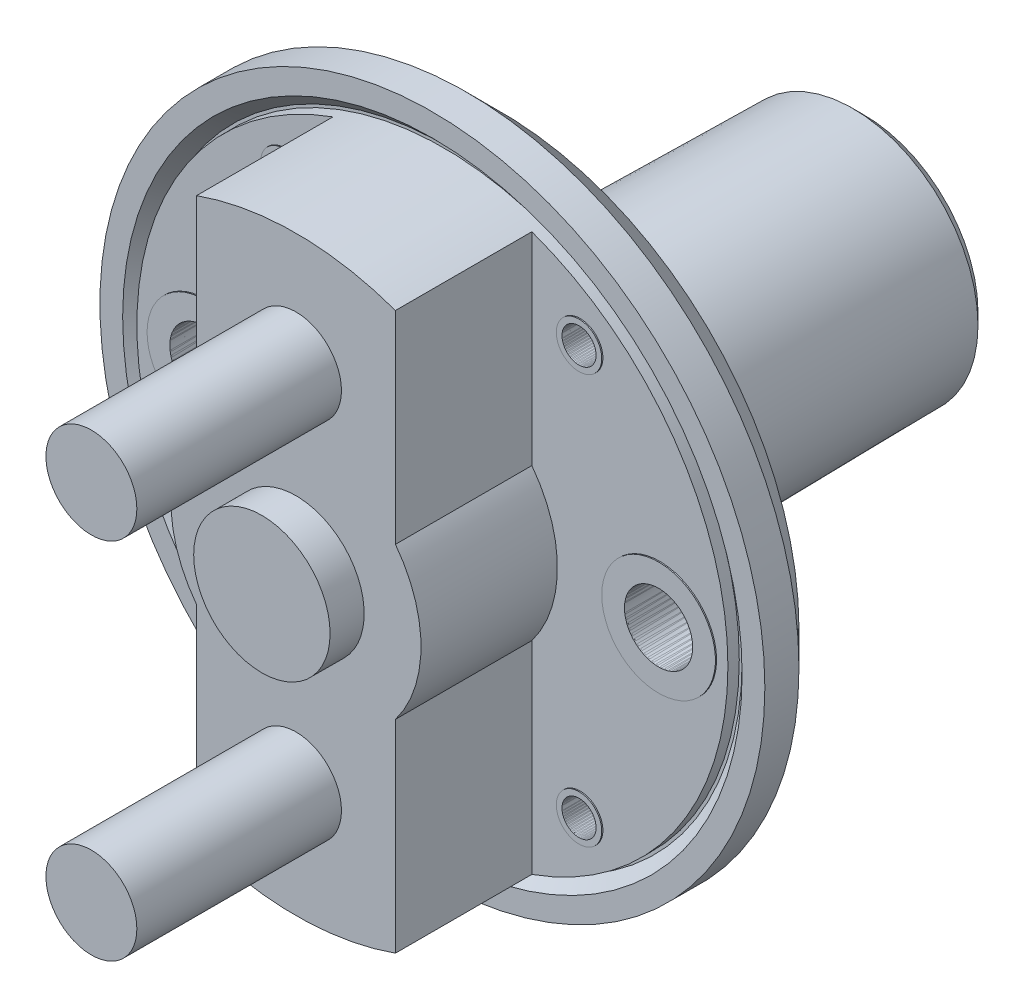
SolidWorks part; units mm, degrees
material "ABS"
ref_plane "正面" through (0, 0, 0) normal (0, 0, 1) x (1, 0, 0)
ref_plane "平面" through (0, 0, 0) normal (0, 1, 0) x (1, 0, 0)
ref_plane "右側面" through (0, 0, 0) normal (1, 0, 0) x (0, 0, -1)
sketch "ｽｹｯﾁ1" plane through (0, 0, 0) normal (0, 0, 1) x (1, 0, 0)
  circle A0 centre (0, 0) radius 11
ref_plane "平面1" through (0, 0, 32) normal (0, 0, 1) x (1, 0, 0)
sketch "ｽｹｯﾁ2" plane through (0, 0, 32) normal (0, 0, 1) x (1, 0, 0)
  circle A0 centre (0, 0) radius 11.5
loft "ﾛﾌﾄ1" add profiles "ｽｹｯﾁ1", "ｽｹｯﾁ2" connector at (1.2963, 10.9233, 0) connector at (0.0939, 11.4996, 32)
sketch "ｽｹｯﾁ3" plane through (0, 0, 0) normal (0, 0, -1) x (-1, 0, 0)
  line L0 (0, 0) -> (2.5, 0) construction
  line L1 (0, 0) -> (-2.5, 0) construction
  line L2 (-2.5, 0) -> (-2.5, -4.899) construction
  line L3 (2.5, 0) -> (2.5, -4.899) construction
  line L4 (-2.5, -4.899) -> (-2.5, -7.899)
  line L5 (-2.5, -7.899) -> (2.5, -7.899)
  line L6 (2.5, -7.899) -> (2.5, -4.899)
  circle A0 centre (0, 0) radius 5.5
extrude "ｶｯﾄ - 押し出し1" cut sketch "ｽｹｯﾁ3" against normal blind 14.5 contours A0 | A0 L4 L5 L6 region at (0, -6.5955, 0) region at (0, 0, 0)
chamfer "面取り1" distance 1 angle 45 1 edges at (11, 0, 0) first distance on face at (0, -3.7992, 0)
chamfer "面取り2" distance 0.5 angle 45 4 edges at (-2.5, -6.399, 0) (0, -7.899, 0) (2.5, -6.399, 0) (0, 5.5, 0)
sketch "ｽｹｯﾁ4" plane through (0, 0, 32) normal (0, 0, 1) x (1, 0, 0)
  circle A0 centre (0, 0) radius 29.25
extrude "ﾎﾞｽ - 押し出し1" add sketch "ｽｹｯﾁ4" along normal blind 6
chamfer "面取り3" distance 3 angle 45 1 edges at (29.25, 0, 32)
sketch "ｽｹｯﾁ5" plane through (0, 0, 38) normal (0, 0, 1) x (1, 0, 0)
  circle A0 centre (0, 0) radius 26
  circle A1 centre (0, 0) radius 26.25
extrude "ｶｯﾄ - 押し出し2" cut sketch "ｽｹｯﾁ5" against normal blind 1
chamfer "面取り4" distance 1 angle 45 1 edges at (26.25, 0, 38)
sketch "ｽｹｯﾁ6" plane through (0, 0, 38) normal (0, 0, 1) x (1, 0, 0)
  line L0 (8.75, 6.6661) -> (8.75, 24.4834)
  line L1 (-8.75, 6.6661) -> (-8.75, 24.4834)
  line L2 (-8.75, -24.4834) -> (-8.75, -6.6661)
  line L4 (8.75, -24.4834) -> (8.75, -6.6661)
  line L5 (-8.75, -24.4834) -> (8.75, 24.4834) construction
  line L6 (-8.75, 24.4834) -> (8.75, -24.4834) construction
  circle A0 centre (0, 0) radius 26 construction
  arc A1 (-8.75, 24.4834) -> (8.75, 24.4834) centre (0, 0) cw
  arc A2 (-8.75, -24.4834) -> (8.75, -24.4834) centre (0, 0) ccw
  arc A3 (-8.75, 6.6661) -> (-8.75, -6.6661) centre (0, 0) ccw
  arc A4 (8.75, -6.6661) -> (8.75, 6.6661) centre (0, 0) ccw
  point P0 (0, 0)
extrude "ﾎﾞｽ - 押し出し2" add sketch "ｽｹｯﾁ6" along normal blind 12
sketch "ｽｹｯﾁ7" plane through (0, 0, 50) normal (0, 0, 1) x (1, 0, 0)
  circle A0 centre (0, 0) radius 6
extrude "ﾎﾞｽ - 押し出し3" add sketch "ｽｹｯﾁ7" along normal blind 3
sketch "ｽｹｯﾁ8" plane through (0, 0, 50) normal (0, 0, 1) x (1, 0, 0)
  line L0 (0, 0) -> (0, 16) construction
  line L1 (0, 0) -> (0, -16) construction
  circle A0 centre (0, 16) radius 4
  circle A1 centre (0, -16) radius 4
extrude "ﾎﾞｽ - 押し出し4" add sketch "ｽｹｯﾁ8" along normal blind 18 separate body
sketch "ｽｹｯﾁ10" plane through (0, 0, 32) normal (0, 0, -1) x (-1, 0, 0)
  line L0 (0, 0) -> (20, 0) construction
  line L1 (-13, -18) -> (13, -18)
  line L2 (-13, -18) -> (-13, 18)
  line L3 (-13, 18) -> (13, 18)
  line L4 (13, -18) -> (13, 18)
  line L5 (-13, -18) -> (13, 18) construction
  line L6 (-13, 18) -> (13, -18) construction
  line L7 (0, 0) -> (-20, 0) construction
  circle A0 centre (13, 18) radius 1.5
  circle A1 centre (-13, 18) radius 1.5
  circle A2 centre (-13, -18) radius 1.5
  circle A3 centre (13, -18) radius 1.5
  circle A4 centre (-20, 0) radius 3
  circle A5 centre (20, 0) radius 3
  point P0 (0, 0)
extrude "ｶｯﾄ - 押し出し4" cut sketch "ｽｹｯﾁ10" against normal through all contours A4 | A1 | A0 | A5 | A3 | A2
sketch "ｽｹｯﾁ11" plane through (0, 0, 32) normal (0, 0, -1) x (-1, 0, 0)
  circle A0 centre (20, 0) radius 3
  circle A1 centre (-20, 0) radius 3
  circle A2 centre (-13, 18) radius 1.5
  circle A3 centre (13, 18) radius 1.5
  circle A4 centre (13, -18) radius 1.5
  circle A5 centre (-13, -18) radius 1.5
  circle A6 centre (-20, 0) radius 5
  circle A7 centre (20, 0) radius 5
  circle A8 centre (13, 18) radius 2
  circle A9 centre (-13, 18) radius 2
  circle A10 centre (-13, -18) radius 2
  circle A11 centre (13, -18) radius 2
extrude "ﾎﾞｽ - 押し出し5" add sketch "ｽｹｯﾁ11" against normal blind 6.1 and the other way blind 0.1 separate body
